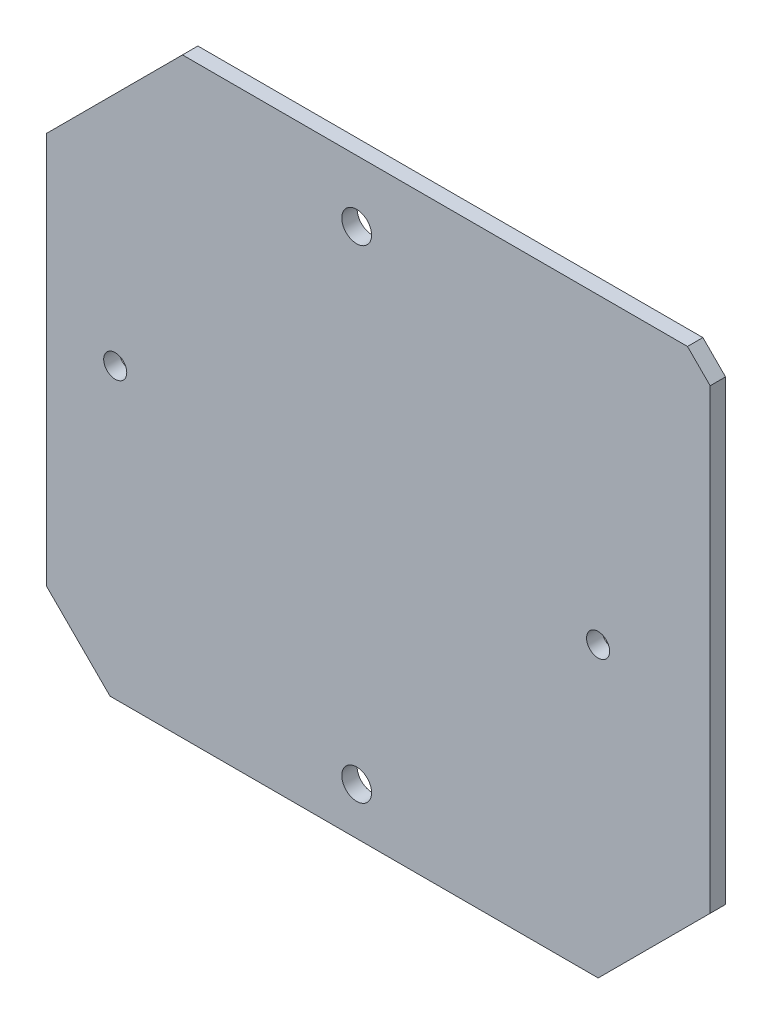
SolidWorks part; units mm, degrees
material "FR4_stuffedProtoboard"
ref_plane "Front Plane" through (0, 0, 0) normal (0, 0, 1) x (1, 0, 0)
ref_plane "Top Plane" through (0, 0, 0) normal (0, 1, 0) x (1, 0, 0)
ref_plane "Right Plane" through (0, 0, 0) normal (1, 0, 0) x (0, 0, -1)
sketch "Imported DXF" plane through (0, 0, 0) normal (0, 0, 1) x (1, 0, 0)
  line L0 (34.372, 27.4613) -> (36.628, 25.2053) construction
  line L1 (36.75, 24.9108) -> (36.75, -22.2441) construction
  line L2 (36.628, -22.5387) -> (25.2053, -33.9613) construction
  line L3 (24.9107, -34.0833) -> (-25.5774, -34.0833) construction
  line L4 (-25.872, -33.9613) -> (-32.2947, -27.5387) construction
  line L5 (-32.4168, -27.2454) -> (-32.429, 13.2331) construction
  line L6 (-32.307, 13.5263) -> (-18.372, 27.4613) construction
  line L7 (-19.8333, 19.5) -> (-19.1667, 19.5) construction
  line L8 (-19.5, 19.8333) -> (-19.5, 19.1667) construction
  line L9 (-19.3333, 19.6667) -> (-18.3333, 20.6667) construction
  line L10 (-19.6667, 19.3333) -> (-20.5833, 18.4167) construction
  line L11 (-19.3333, 19.3333) -> (-18.9167, 18.9167) construction
  line L12 (19.5, 19.8333) -> (19.5, 19.1667) construction
  line L13 (19.8333, 19.5) -> (19.1667, 19.5) construction
  line L14 (19.6667, 19.3333) -> (20.6667, 18.3333) construction
  line L15 (19.3333, 19.6667) -> (18.4167, 20.5833) construction
  line L16 (19.3333, 19.3333) -> (18.9167, 18.9167) construction
  line L17 (-19.8333, -19.5) -> (-19.1667, -19.5) construction
  line L18 (-19.5, -19.8333) -> (-19.5, -19.1667) construction
  line L19 (-19.3333, -19.6667) -> (-18.3333, -20.6667) construction
  line L20 (-19.6667, -19.3333) -> (-20.5833, -18.4167) construction
  line L21 (-19.3333, -19.3333) -> (-18.9167, -18.9167) construction
  line L22 (19.8333, -19.5) -> (19.1667, -19.5) construction
  line L23 (19.5, -19.8333) -> (19.5, -19.1667) construction
  line L24 (19.3333, -19.6667) -> (18.3333, -20.6667) construction
  line L25 (19.6667, -19.3333) -> (20.5833, -18.4167) construction
  line L26 (19.3333, -19.3333) -> (18.9167, -18.9167) construction
  line L27 (31.9857, 21.9857) -> (31.5143, 21.5143) construction
  line L28 (31.9857, 21.5143) -> (31.5143, 21.9857) construction
  line L29 (31.75, 21.5143) -> (31.75, 20.1001) construction
  line L30 (31.75, 21.9857) -> (31.75, 23.2821) construction
  line L31 (31.5143, 21.75) -> (30.9251, 21.75) construction
  line L32 (34.0774, 27.5833) -> (-18.0774, 27.5833) construction
  line L33 (-63.5042, 0) -> (63.5042, 0) construction
  line L34 (0, 54.0232) -> (0, -54.9661) construction
  arc A0 (34.372, 27.4613) -> (34.0774, 27.5833) centre (34.0774, 27.1667) ccw construction
  arc A1 (36.75, 24.9108) -> (36.628, 25.2054) centre (36.3333, 24.9108) ccw construction
  arc A2 (36.628, -22.5387) -> (36.75, -22.2441) centre (36.3333, -22.2441) ccw construction
  arc A3 (24.9107, -34.0833) -> (25.2054, -33.9613) centre (24.9107, -33.6667) ccw construction
  arc A4 (-25.872, -33.9613) -> (-25.5774, -34.0833) centre (-25.5774, -33.6667) ccw construction
  arc A5 (-32.4168, -27.2454) -> (-32.2947, -27.5386) centre (-32.0001, -27.244) ccw construction
  arc A6 (-32.307, 13.5263) -> (-32.4291, 13.2331) centre (-32.0129, 13.2319) ccw construction
  arc A7 (-18.0774, 27.5833) -> (-18.372, 27.4613) centre (-18.0774, 27.1667) ccw construction
  circle A8 centre (-20.9167, 0) radius 1 construction
  circle A9 centre (20.9167, 0) radius 1 construction
  circle A10 centre (0, 20.9167) radius 1.2917 construction
  circle A11 centre (0, -20.9167) radius 1.2917 construction
  point P93 (0, 0)
  dimension "D1" = 2
sketch "Outline" plane through (0, 0, 0) normal (0, 0, 1) x (1, 0, 0)
  line L0 (34.3921, 31.5) -> (36.75, 29.1421)
  line L1 (36.75, 29.1421) -> (36.75, -18.3579)
  line L2 (36.75, -18.3579) -> (25.1079, -30)
  line L3 (25.1079, -30) -> (-25.6421, -30)
  line L4 (-25.6421, -30) -> (-32.25, -23.3921)
  line L5 (-32.25, -23.3921) -> (-32.25, 17.3579)
  line L6 (-32.25, 17.3579) -> (-18.1079, 31.5)
  line L32 (103.1538, 0) -> (-30.8725, 0) construction
  line L33 (0, 82.654) -> (0, -12.3574) construction
  line L34 (34.3921, 31.5) -> (-18.1079, 31.5)
  point P0 (0, 0)
  dimension "D2" = 135
  dimension "D3" = 135
  dimension "D4" = 135
  dimension "D5" = 47.5
  dimension "D6" = 135
  dimension "D7" = 36.75
  dimension "D8" = 30
  dimension "D9" = 50.75
  dimension "D10" = 40.75
  dimension "D11" = 52.5
  dimension "D12" = 20
  dimension "D20" = 69
sketch "Connector locations" plane through (0, 0, 0) normal (0, 0, 1) x (1, 0, 0)
  line L0 (31.8, 27.4) -> (31.8, 24.2)
  line L1 (23.7588, 21.496) -> (21.496, 23.7588)
  line L2 (36.75, 29.1421) -> (36.75, -18.3579) construction
  line L3 (34.3921, 31.5) -> (-18.1079, 31.5) construction
  line L4 (0, 0) -> (22.6274, 22.6274) construction
  line L5 (200103.1538, 0) -> (-200030.8725, 0) construction
  line L6 (21.496, -23.7588) -> (23.7588, -21.496)
  line L7 (-23.7588, -21.496) -> (-21.496, -23.7588)
  line L8 (-21.496, 23.7588) -> (-23.7588, 21.496)
  point P12 (31.8, 25.8)
  dimension "D1" = 4.95
  dimension "D2" = 3.2
  dimension "D3" = 4.1
  dimension "D4" = 32
  dimension "D5" = 4
  dimension "D6" = 3.2
  dimension "D7" = 45
  dimension "D8" = 45
extrude "Boss-Extrude3" add sketch "Outline" against normal blind 1.6
sketch "Hole Locations" plane through (0, 0, 0) normal (0, 0, 1) x (1, 0, 0)
  circle A1 centre (-25.1, 0) radius 1.2 construction
  circle A2 centre (0, 25.1) radius 1.55 construction
  circle A3 centre (25.1, 0) radius 1.2 construction
  circle A4 centre (0, -25.1) radius 1.55 construction
  circle A5 centre (-25.1, 0) radius 1.2
  circle A6 centre (0, 25.1) radius 1.55
  circle A7 centre (25.1, 0) radius 1.2
  circle A8 centre (0, -25.1) radius 1.55
extrude "Cut-Extrude1" cut sketch "Hole Locations" against normal up to next
